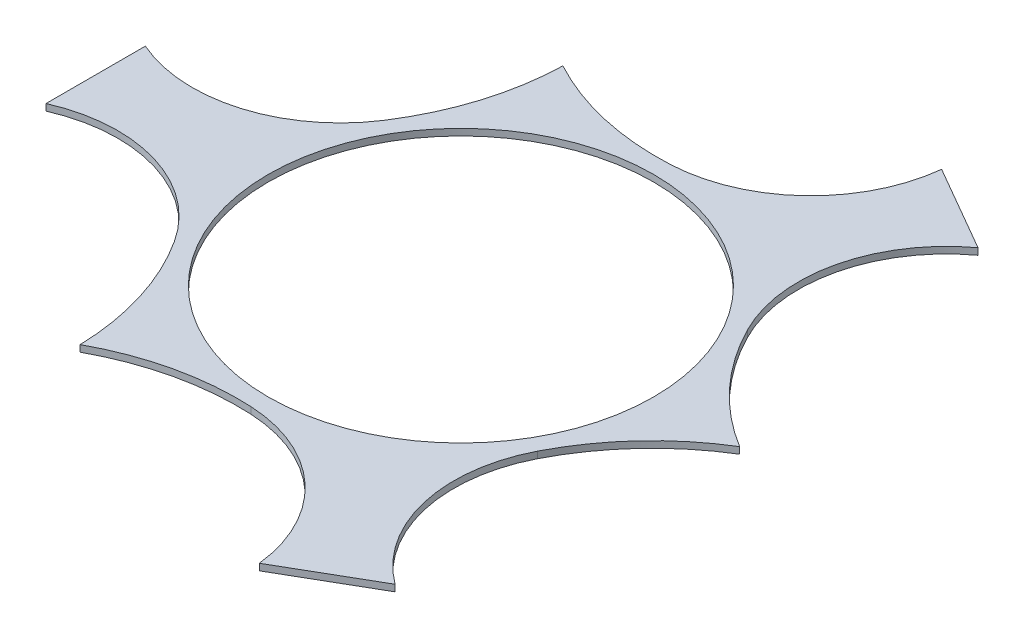
SolidWorks part; units mm, degrees
ref_plane "Front Plane" through (0, 0, 0) normal (0, 0, 1) x (1, 0, 0)
ref_plane "Top Plane" through (0, 0, 0) normal (0, 1, 0) x (1, 0, 0)
ref_plane "Right Plane" through (0, 0, 0) normal (1, 0, 0) x (0, 0, -1)
sketch "Sketch1" plane through (0, 0, 0) normal (0, 1, 0) x (1, 0, 0)
  line L0 (0, 0) -> (-351.3249, 0) construction
  line L1 (-115, 199.1858) -> (-230, 0) construction
  line L2 (-230, 0) -> (-115, -199.1858) construction
  line L3 (-115, -199.1858) -> (115, -199.1858) construction
  line L4 (115, -199.1858) -> (230, 0) construction
  line L5 (230, 0) -> (115, 199.1858) construction
  line L6 (115, 199.1858) -> (-115, 199.1858) construction
  line L7 (-351.3249, -47.7802) -> (-351.3249, 47.7802) construction
  line L8 (-172.5, 99.5929) -> (-250.0865, 144.3875) construction
  line L9 (0, 0) -> (-174.5811, 302.3833) construction
  line L10 (-351.3249, -47.7802) -> (-351.3249, 47.7802)
  line L11 (134.2836, 328.1464) -> (217.0413, 280.3662)
  line L12 (217.0413, -280.3662) -> (134.2836, -328.1464)
  circle A0 centre (0, 0) radius 199.1858 construction
  arc A1 (-351.3249, 47.7802) -> (-174.6997, 100.8629) centre (-294.2288, 178.19) ccw
  arc A2 (-174.6997, 100.8629) -> (-134.05, 232.1814) centre (-387.963, 238.8295) ccw
  arc A3 (-351.3249, -47.7802) -> (-174.6997, -100.8629) centre (-294.2288, -178.19) cw
  arc A4 (-174.6997, -100.8629) -> (-134.05, -232.1814) centre (-387.963, -238.8295) cw
  arc A5 (134.2836, 328.1464) -> (0, 201.7258) centre (-7.2026, 343.9046) cw
  arc A6 (217.0413, 280.3662) -> (174.6997, 100.8629) centre (301.4314, 165.7146) ccw
  arc A7 (0, 201.7258) -> (-134.05, 232.1814) centre (-12.8509, 455.4005) cw
  arc A8 (174.6997, 100.8629) -> (268.1, 0) centre (400.8139, 216.5711) ccw
  arc A9 (217.0413, -280.3662) -> (174.6997, -100.8629) centre (301.4314, -165.7146) cw
  arc A10 (134.2836, -328.1464) -> (0, -201.7258) centre (-7.2026, -343.9046) ccw
  arc A11 (174.6997, -100.8629) -> (268.1, 0) centre (400.8139, -216.5711) cw
  arc A12 (0, -201.7258) -> (-134.05, -232.1814) centre (-12.8509, -455.4005) ccw
  circle A13 centre (0, 0) radius 185.3996
  point P46 (0, 0)
  dimension "D4" = 254
  dimension "D8" = 370.7992
  dimension "D1" = 230
  dimension "D2" = 95.5604
  dimension "D3" = 351.3249
  dimension "D5" = 2.54
  dimension "D6" = 38.1
  dimension "D7" = 3
extrude "Boss-Extrude1" add sketch "Sketch1" along normal blind 6.35
ref_axis "Axis1" through (0, 0, 0) along (0, 1, 0)
